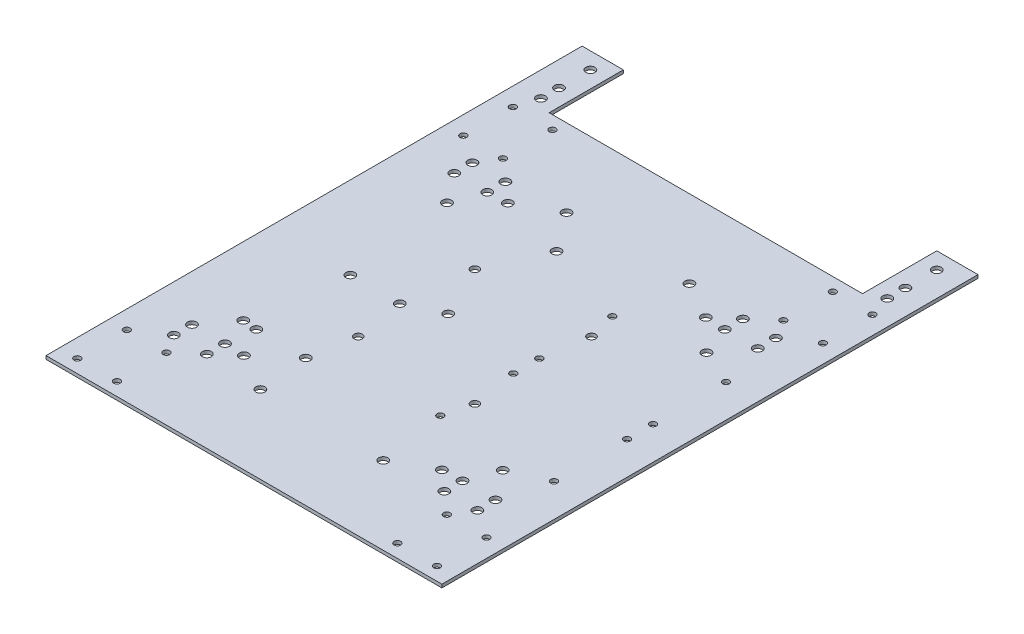
SolidWorks part; units mm, degrees
ref_plane "前视基准面" through (0, 0, 0) normal (0, 0, 1) x (1, 0, 0)
ref_plane "上视基准面" through (0, 0, 0) normal (0, 1, 0) x (1, 0, 0)
ref_plane "右视基准面" through (0, 0, 0) normal (1, 0, 0) x (0, 0, -1)
sketch "草图2" plane through (0, 0, 0) normal (0, 1, 0) x (1, 0, 0)
  line L0 (-120, 140) -> (-120, 185)
  line L1 (-95, 140) -> (95, 140)
  line L2 (-120, 140) -> (-120, -140)
  line L3 (-120, -140) -> (120, -140)
  line L4 (120, 140) -> (120, -140)
  line L5 (-120, 140) -> (120, -140) construction
  line L6 (-120, -140) -> (120, 140) construction
  line L7 (-120, 185) -> (-95, 185)
  line L8 (-95, 185) -> (-95, 140)
  line L9 (0, 140) -> (0, 250.6324) construction
  line L10 (95, 185) -> (95, 140)
  line L11 (120, 140) -> (120, 185)
  line L12 (120, 185) -> (95, 185)
  point P0 (0, 0)
  dimension "D1" = 280
  dimension "D2" = 240
  dimension "D3" = 190
  dimension "D4" = 45
base flange "基体-法兰2" sketch "草图2" thickness 2 reverse thickness direction no parameters "D1"=2.7366
sketch "草图26" plane through (0, 0, 0) normal (0, 1, 0) x (1, 0, 0)
  line L0 (-109, 117) -> (-85, 117) construction
  line L1 (-97, 110.9114) -> (-97, 117) construction
  line L2 (-120, 185) -> (-120, -140) construction
  line L3 (95, 140) -> (-95, 140) construction
  line L4 (0, 0) -> (-116.7374, 0) construction
  line L5 (0, 0) -> (0, 140) construction
  line L6 (-97, -110.9114) -> (-97, -117) construction
  line L7 (-109, -117) -> (-85, -117) construction
  line L8 (97, 110.9114) -> (97, 117) construction
  line L9 (109, 117) -> (85, 117) construction
  line L10 (109, -117) -> (85, -117) construction
  line L11 (97, -110.9114) -> (97, -117) construction
  circle A0 centre (-109, 102) radius 2
  circle A1 centre (-109, 132) radius 2
  circle A2 centre (-85, 132) radius 2
  circle A3 centre (-85, 102) radius 2
  circle A4 centre (-85, -102) radius 2
  circle A5 centre (-85, -132) radius 2
  circle A6 centre (-109, -132) radius 2
  circle A7 centre (-109, -102) radius 2
  circle A8 centre (85, 102) radius 2
  circle A9 centre (85, 132) radius 2
  circle A10 centre (109, 132) radius 2
  circle A11 centre (109, 102) radius 2
  circle A12 centre (109, -102) radius 2
  circle A13 centre (109, -132) radius 2
  circle A14 centre (85, -132) radius 2
  circle A15 centre (85, -102) radius 2
  dimension "D2" = 4
  dimension "D1" = 30
  dimension "D3" = 24
  dimension "D4" = 15
  dimension "D5" = 23
  dimension "D6" = 23
extrude "切除-拉伸1" cut sketch "草图26" against normal through all normal cut yes
sketch "草图27" plane through (0, -2, 0) normal (0, -1, 0) x (1, 0, 0)
  line L0 (0, 0) -> (0, 130.6645) construction
  line L2 (-35.3553, 35.3553) -> (0, 0) construction
  circle A0 centre (0, 0) radius 50 construction
  circle A1 centre (-35.3553, 35.3553) radius 2.5
  circle A2 centre (35.3553, 35.3553) radius 2.5
  circle A3 centre (35.3553, -35.3553) radius 2.5
  circle A4 centre (-35.3553, -35.3553) radius 2.5
  point P17 (0, 0)
  dimension "D1" = 100
  dimension "D2" = 5
  dimension "D3" = 45
  dimension "D4" = 4
extrude "切除-拉伸2" cut sketch "草图27" against normal blind 10 normal cut yes
sketch "草图28" plane through (0, -2, 0) normal (0, -1, 0) x (1, 0, 0)
  line L0 (0, 0) -> (119.9543, 0) construction
  line L2 (0, 0) -> (0, -100) construction
  circle A0 centre (0, 0) radius 100 construction
  circle A1 centre (-60, -80) radius 2.75
  circle A2 centre (-37.25, -92.8032) radius 2.75
  circle A3 centre (-78.6611, -61.7449) radius 2.75
  circle A4 centre (78.6611, -61.7449) radius 2.75
  circle A5 centre (37.25, -92.8032) radius 2.75
  circle A6 centre (60, -80) radius 2.75
  circle A7 centre (-78.6611, 61.7449) radius 2.75
  circle A8 centre (-37.25, 92.8032) radius 2.75
  circle A9 centre (-60, 80) radius 2.75
  circle A10 centre (60, 80) radius 2.75
  circle A11 centre (37.25, 92.8032) radius 2.75
  circle A12 centre (78.6611, 61.7449) radius 2.75
  point P13 (0, 0)
  point P16 (0, 0)
  dimension "D1" = 200
  dimension "D2" = 5.5
  dimension "D4" = 2
  dimension "D5" = 2
extrude "切除-拉伸3" cut sketch "草图28" against normal blind 10 normal cut yes
ref_plane "基准面1" through (95, 0, -140) normal (-1, 0, 0) x (0, 0, 1)
sketch "草图29" plane through (0, -2, 0) normal (0, -1, 0) x (1, 0, 0)
  line L0 (120, -185) -> (95, -185) construction
  line L1 (105, -145) -> (105, -175) construction
  line L2 (120, 140) -> (120, -185) construction
  circle A0 centre (105, -175) radius 2.75
  circle A1 centre (105, -156) radius 2.75
  circle A2 centre (105, -145) radius 2.75
  point P8 (0, 0)
  point P9 (0, 0)
  dimension "D4" = 5.5
  dimension "D1" = 10
  dimension "D2" = 19
  dimension "D3" = 11
  dimension "D5" = 15
extrude "切除-拉伸4" cut sketch "草图29" against normal blind 10 normal cut yes
mirror "镜向1" about plane through (0, 0, 0) normal (1, 0, 0) of "切除-拉伸4"
sketch "草图30" plane through (0, 0, 0) normal (0, 1, 0) x (1, 0, 0)
  line L0 (-35.7101, 85) -> (-96.3912, 85) construction
  line L1 (-120, 185) -> (-120, -140) construction
  circle A0 centre (-92, 90.5) radius 2.75
  circle A1 centre (-92, 79.5) radius 2.75
  circle A2 centre (-72, 79.5) radius 2.75
  circle A3 centre (-72, 90.5) radius 2.75
  dimension "D4" = 5.5
  dimension "D1" = 11
  dimension "D2" = 85
  dimension "D5" = 28
  dimension "D3" = 2
extrude "切除-拉伸5" cut sketch "草图30" against normal blind 10 normal cut yes
mirror "镜向2" about plane through (0, 0, 0) normal (0, 0, 1) of "切除-拉伸5"
mirror "镜向3" about plane through (0, 0, 0) normal (1, 0, 0) of "镜向2", "切除-拉伸5"
sketch "草图31" plane through (0, 0, 0) normal (0, 1, 0) x (1, 0, 0)
  line L0 (100, -29.87) -> (31.05, -29.87) construction
  line L1 (65.525, -29.87) -> (65.525, -52) construction
  line L4 (120, -140) -> (120, 185) construction
  circle A0 centre (31.05, -52) radius 2
  circle A1 centre (31.05, -7.74) radius 2
  circle A2 centre (100, -7.74) radius 2
  circle A3 centre (100, -52) radius 2
  circle A4 centre (-92, -79.5) radius 2.75 construction
  point P12 (30.8716, -29.87)
  point P13 (69.9763, -29.87)
  point P16 (-31.05, -29.87)
  point P17 (-100, -29.87)
  point P18 (0, 0)
  dimension "D4" = 27.5
  dimension "D5" = 4
  dimension "D1" = 44.26
  dimension "D2" = 68.95
  dimension "D3" = 20
extrude "切除-拉伸6" cut sketch "草图31" against normal blind 10 normal cut yes
pattern_linear "阵列(线性)1" count 2 spacing 60 along (0, 0, -1) of "切除-拉伸6"
sketch "草图32" plane through (0, 0, 0) normal (0, 1, 0) x (1, 0, 0)
  line L0 (-40, 36.65) -> (-20, 36.65) construction
  line L1 (-120, 185) -> (-120, -140) construction
  circle A0 centre (-20, 69.5) radius 2.75
  circle A1 centre (-20, 3.8) radius 2.75
  circle A2 centre (-72, 79.5) radius 2.75 construction
  point P8 (-30.1244, 14.9471)
  point P9 (-59.1424, 13.1299)
  point P10 (0, 0)
  dimension "D3" = 5.5
  dimension "D1" = 100
  dimension "D2" = 20
  dimension "D4" = 65.7
  dimension "D5" = 10
extrude "切除-拉伸7" cut sketch "草图32" against normal blind 10 normal cut yes
sketch "草图33" plane through (0, 0, 0) normal (0, 1, 0) x (1, 0, 0)
  line L0 (-40, -34) -> (-120, -34) construction
  line L1 (-120, 185) -> (-120, -140) construction
  line L2 (-120, 185) -> (-120, -140) construction
  circle A0 centre (-70, -62.5) radius 2.75
  circle A1 centre (-70, -5.5) radius 2.75
  circle A2 centre (-40, -5.5) radius 2.75
  circle A3 centre (-40, -62.5) radius 2.75
  circle A4 centre (-92, -79.5) radius 2.75 construction
  point P16 (0, 0)
  dimension "D1" = 57
  dimension "D2" = 5.5
  dimension "D4" = 17
  dimension "D5" = 50
  dimension "D3" = 2
extrude "切除-拉伸8" cut sketch "草图33" against normal blind 10 normal cut yes
sketch "折弯-线3" plane through (0, 0, 0) normal (0, 1, 0) x (1, 0, 0)
sketch "边界框3" plane through (0, 0, 0) normal (0, 1, 0) x (1, 0, 0)
sheet metal parameters "钣金7" thickness 2 parameters "D1"=2.7366
flat pattern "平板型式7" [suppressed]
sketch "折弯-线4" plane through (0, 0, 0) normal (0, 1, 0) x (1, 0, 0)
sketch "边界框4" [suppressed] plane through (0, 0, 0) normal (0, 1, 0) x (1, 0, 0)
sheet metal parameters "钣金12" thickness 2 parameters "D1"=2.7366
flat pattern "平板型式7"
sketch "折弯-线4" plane through (0, 0, 0) normal (0, 1, 0) x (1, 0, 0)
sketch "边界框4" [suppressed] plane through (0, 0, 0) normal (0, 1, 0) x (1, 0, 0)
sheet metal parameters "钣金13" thickness 2 parameters "D1"=2.7366
flat pattern "平板型式7"
sketch "折弯-线4" plane through (0, 0, 0) normal (0, 1, 0) x (1, 0, 0)
sketch "边界框4" [suppressed] plane through (0, 0, 0) normal (0, 1, 0) x (1, 0, 0)
sheet metal parameters "钣金14" thickness 2 parameters "D1"=2.7366
flat pattern "平板型式7"
sketch "折弯-线4" plane through (0, 0, 0) normal (0, 1, 0) x (1, 0, 0)
sketch "边界框4" [suppressed] plane through (0, 0, 0) normal (0, 1, 0) x (1, 0, 0)
sheet metal parameters "钣金26" thickness 2 parameters "D1"=2.7366
flat pattern "平板型式7"
sketch "折弯-线4" plane through (0, 0, 0) normal (0, 1, 0) x (1, 0, 0)
sketch "边界框4" [suppressed] plane through (0, 0, 0) normal (0, 1, 0) x (1, 0, 0)
sheet metal parameters "钣金27" thickness 2 parameters "D1"=2.7366
flat pattern "平板型式7"
sketch "折弯-线4" plane through (0, 0, 0) normal (0, 1, 0) x (1, 0, 0)
sketch "边界框4" [suppressed] plane through (0, 0, 0) normal (0, 1, 0) x (1, 0, 0)
sheet metal parameters "钣金28" thickness 2 parameters "D1"=2.7366
flat pattern "平板型式7"
sketch "折弯-线4" plane through (0, 0, 0) normal (0, 1, 0) x (1, 0, 0)
sketch "边界框4" [suppressed] plane through (0, 0, 0) normal (0, 1, 0) x (1, 0, 0)
sheet metal parameters "钣金29" thickness 2 parameters "D1"=2.7366
flat pattern "平板型式7"
sketch "折弯-线4" plane through (0, 0, 0) normal (0, 1, 0) x (1, 0, 0)
sketch "边界框4" [suppressed] plane through (0, 0, 0) normal (0, 1, 0) x (1, 0, 0)
sheet metal parameters "钣金30" thickness 2 parameters "D1"=2.7366
flat pattern "平板型式7"
sketch "折弯-线4" plane through (0, 0, 0) normal (0, 1, 0) x (1, 0, 0)
sketch "边界框4" [suppressed] plane through (0, 0, 0) normal (0, 1, 0) x (1, 0, 0)
sheet metal parameters "钣金31" thickness 2 parameters "D1"=2.7366
flat pattern "平板型式7"
sketch "折弯-线4" plane through (0, 0, 0) normal (0, 1, 0) x (1, 0, 0)
sketch "边界框4" [suppressed] plane through (0, 0, 0) normal (0, 1, 0) x (1, 0, 0)
sheet metal parameters "钣金32" thickness 2 parameters "D1"=2.7366
flat pattern "平板型式7"
sketch "折弯-线4" plane through (0, 0, 0) normal (0, 1, 0) x (1, 0, 0)
sketch "边界框4" [suppressed] plane through (0, 0, 0) normal (0, 1, 0) x (1, 0, 0)
sheet metal parameters "钣金33" thickness 2 parameters "D1"=2.7366
flat pattern "平板型式7"
sketch "折弯-线4" plane through (0, 0, 0) normal (0, 1, 0) x (1, 0, 0)
sketch "边界框4" [suppressed] plane through (0, 0, 0) normal (0, 1, 0) x (1, 0, 0)
sheet metal parameters "钣金34" thickness 2 parameters "D1"=2.7366
flat pattern "平板型式7"
sketch "折弯-线4" plane through (0, 0, 0) normal (0, 1, 0) x (1, 0, 0)
sketch "边界框4" [suppressed] plane through (0, 0, 0) normal (0, 1, 0) x (1, 0, 0)
